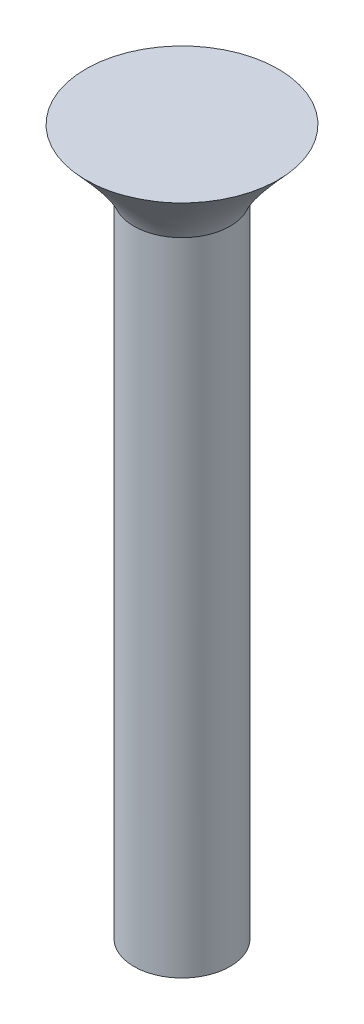
SolidWorks part; units mm, degrees
ref_plane "Front Plane" through (0, 0, 0) normal (0, 0, 1) x (1, 0, 0)
ref_plane "Top Plane" through (0, 0, 0) normal (0, 1, 0) x (1, 0, 0)
ref_plane "Right Plane" through (0, 0, 0) normal (1, 0, 0) x (0, 0, -1)
sketch "Sketch1" plane through (0, 0, 0) normal (0, 1, 0) x (1, 0, 0)
  circle A0 centre (0, 0) radius 1.5
  dimension "D1" = 3
extrude "Boss-Extrude1" add sketch "Sketch1" along normal blind 20
ref_plane "Plane1" through (0, 22, 0) normal (0, 1, 0) x (1, 0, 0)
sketch "Sketch2" plane through (0, 22, 0) normal (0, 1, 0) x (1, 0, 0)
  circle A0 centre (0, 0) radius 3
  dimension "D1" = 6
sketch "Sketch3" plane through (0, 20, 0) normal (0, 1, 0) x (1, 0, 0)
  circle A1 centre (0, 0) radius 1.5
  circle A2 centre (0, 0) radius 1.5
  dimension "D1" = 0
loft "Loft1" add profiles "Sketch3", "Sketch2" connector at (-1.3671, 20, -0.6173) connector at (-1.3519, 22, -2.6781)
